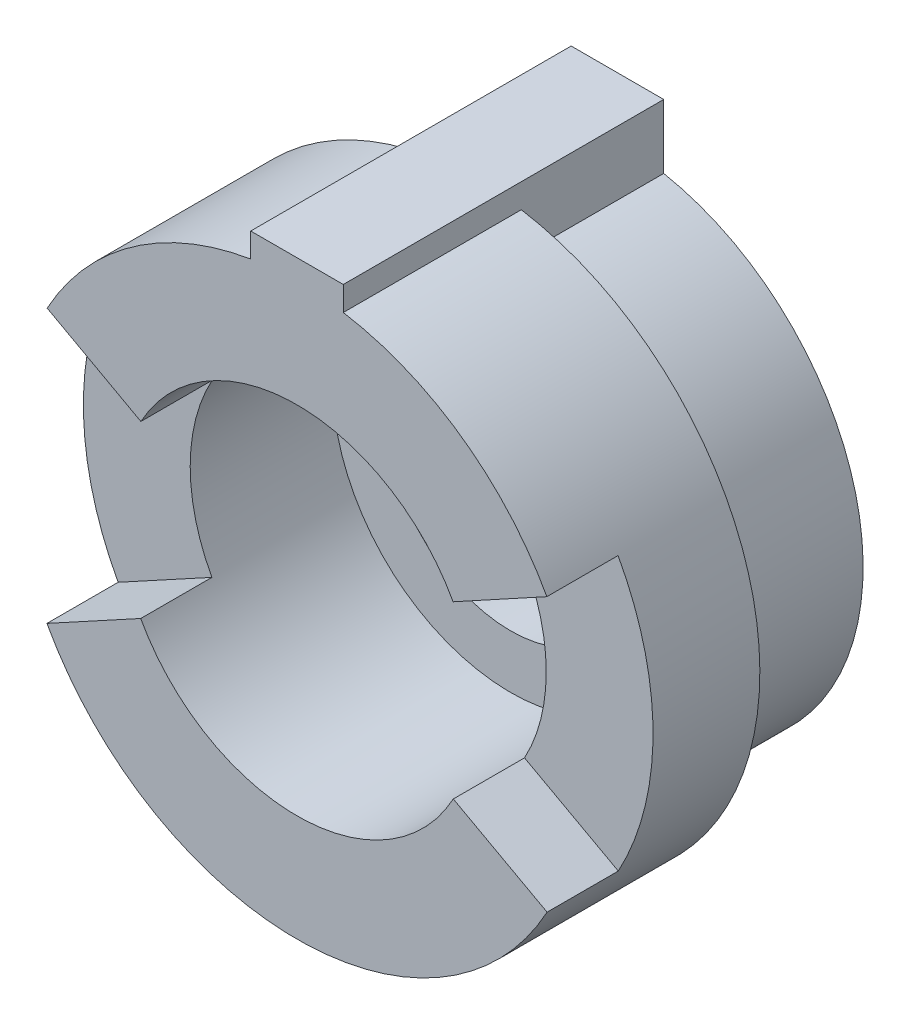
SolidWorks part; units mm, degrees
ref_plane "Front Plane" through (0, 0, 0) normal (0, 0, 1) x (1, 0, 0)
ref_plane "Top Plane" through (0, 0, 0) normal (0, 1, 0) x (1, 0, 0)
ref_plane "Right Plane" through (0, 0, 0) normal (1, 0, 0) x (0, 0, -1)
sketch "Sketch1" plane through (0, 0, 0) normal (0, 0, 1) x (1, 0, 0)
  circle A0 centre (0, 0) radius 8
  circle A1 centre (0, 0) radius 3.5
  dimension "D1" = 7
  dimension "D2" = 16
extrude "Boss-Extrude1" add sketch "Sketch1" along normal blind 3
sketch "Sketch2" plane through (0, 0, 3) normal (0, 0, 1) x (1, 0, 0)
  circle A0 centre (0, 0) radius 8
  circle A1 centre (0, 0) radius 5
  dimension "D1" = 16
  dimension "D2" = 10
extrude "Boss-Extrude2" add sketch "Sketch2" along normal blind 6
sketch "Sketch4" plane through (0, 0, 0) normal (0, 1, 0) x (1, 0, 0)
  line L0 (-8.56, -9) -> (-8.56, -7)
  line L1 (-16.56, -9) -> (-8.56, -9)
  line L2 (8.56, -9) -> (8.56, -7)
  line L3 (8.56, -9) -> (16.56, -9)
  line L4 (-16.56, -9) -> (-16.56, -7)
  line L5 (-16.56, -7) -> (-8.56, -7)
  line L6 (16.56, -9) -> (16.56, -7)
  line L7 (16.56, -7) -> (8.56, -7)
  dimension "D1" = 7
  dimension "D2" = 8.56
  dimension "D3" = 2
  dimension "D4" = 8.56
  dimension "D5" = 8
  dimension "D6" = 8
  dimension "D7" = 2
  dimension "D8" = 7
wrap "Wrap3" sketch "Sketch4" wrap type deboss source sketch "Sketch4" thickness 4 face at (8, 0, 0) parameters "D1"=4
sketch "Sketch5" plane through (0, 0, 0) normal (0, 0, -1) x (-1, 0, 0)
  line L0 (-1.3, 6.7764) -> (-1.3, 7.8937)
  line L2 (1.3, 7.8937) -> (1.3, 6.7764)
  arc A0 (-1.3, 7.8937) -> (1.3, 7.8937) centre (0, 0) ccw
  arc A1 (-1.3, 6.7764) -> (1.3, 6.7764) centre (0, 0) ccw
  circle A2 centre (0, 0) radius 8 construction
  dimension "D3" = 6.9
  dimension "D1" = 8
  dimension "D2" = 1.3
extrude "Cut-Extrude1" cut sketch "Sketch5" against normal blind 4
sketch "Sketch6" plane through (0, 0, 0) normal (0, 0, -1) x (-1, 0, 0)
  line L0 (-1.3, 7.7971) -> (-1.3, 8.5764)
  line L1 (-1.3, 8.5764) -> (1.3, 8.5764)
  line L2 (1.3, 8.5764) -> (1.3, 7.7971)
  line L3 (-1.3, 6.7764) -> (-1.3, 7.8937) construction
  arc A0 (1.3, 7.7971) -> (-1.3, 7.7971) centre (0, -0.0965) ccw
  dimension "D1" = 8
  dimension "D2" = 1.3
  dimension "D3" = 1.0207
  dimension "D4" = 1.8
extrude "Boss-Extrude3" add sketch "Sketch6" against normal blind 9
equation "\"D3@Sketch5\"= 7 - \"tol1@parametersSketch@prostheticParameters.SLDPRT\" / 2"
equation "\"D2@Sketch5\"= 1.5 - \"tol2@parametersSketch@prostheticParameters.SLDPRT\""
equation "\"D2@Sketch6\"= 1.5 - \"tol2@parametersSketch@prostheticParameters.SLDPRT\""
equation "\"D4@Sketch6\"= 2 - \"tol2@parametersSketch@prostheticParameters.SLDPRT\""
